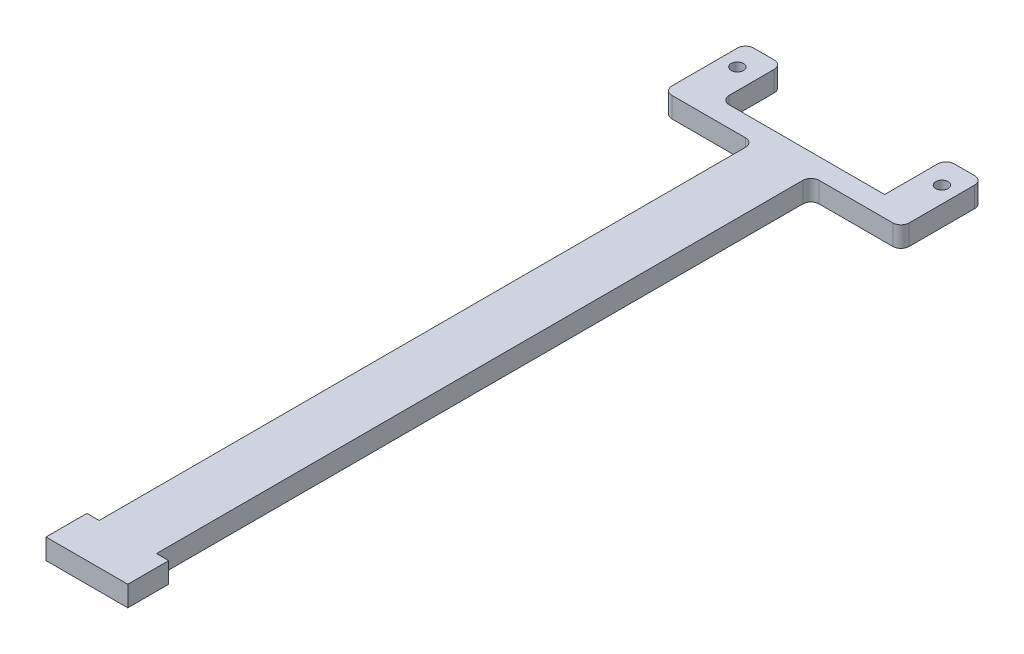
SolidWorks part; units mm, degrees
ref_plane "Front Plane" through (0, 0, 0) normal (0, 0, 1) x (1, 0, 0)
ref_plane "Top Plane" through (0, 0, 0) normal (0, 1, 0) x (1, 0, 0)
ref_plane "Right Plane" through (0, 0, 0) normal (1, 0, 0) x (0, 0, -1)
sketch "Sketch1" plane through (0, 0, 0) normal (0, 1, 0) x (1, 0, 0)
  line L1 (9, -10) -> (9, 0)
  line L2 (9, 0) -> (6, 0)
  line L3 (6, 0) -> (6, 160)
  line L4 (6, 160) -> (28, 160)
  line L5 (28, 160) -> (28, 180)
  line L6 (28, 180) -> (-30, 180)
  line L7 (-30, 180) -> (-30, 160)
  line L8 (-30, 160) -> (-8, 160)
  line L9 (-8, 160) -> (-8, 0)
  line L10 (-8, 0) -> (-11, 0)
  line L11 (-11, 0) -> (-11, -10)
  line L13 (-11, -10) -> (9, -10)
  dimension "D1" = 20
  dimension "D2" = 160
  dimension "D3" = 10
  dimension "D4" = 14
  dimension "D5" = 3
  dimension "D6" = 58
  dimension "D7" = 22
  dimension "D8" = 20
  dimension "D9" = 10
  dimension "D10" = 6
extrude "Boss-Extrude1" add sketch "Sketch1" along normal blind 5
sketch "Sketch2" plane through (0, 5, 0) normal (0, 1, 0) x (1, 0, 0)
  line L0 (-30, 180) -> (-30, 160) construction
  line L1 (28, 180) -> (-30, 180) construction
  line L2 (-21, 180) -> (-21, 165)
  line L3 (-21, 165) -> (19, 165)
  line L4 (19, 165) -> (19, 180)
  line L5 (-21, 180) -> (19, 180)
  circle A0 centre (-26, 174) radius 1.5
  circle A1 centre (24, 174) radius 1.5
  dimension "D1" = 3
  dimension "D2" = 3
  dimension "D3" = 50
  dimension "D4" = 4
  dimension "D5" = 6
  dimension "D6" = 6
  dimension "D7" = 40
  dimension "D8" = 15
  dimension "D9" = 9
extrude "Cut-Extrude1" cut sketch "Sketch2" against normal blind 10
fillet "Fillet1" radius 2 9 edges at (6, 2.5, -160) (-8, 2.5, -160) (-30, 2.5, -160) (28, 2.5, -160) (28, 2.5, -180) (19, 2.5, -180) (-21, 2.5, -165) (-21, 2.5, -180) (-30, 2.5, -180)
